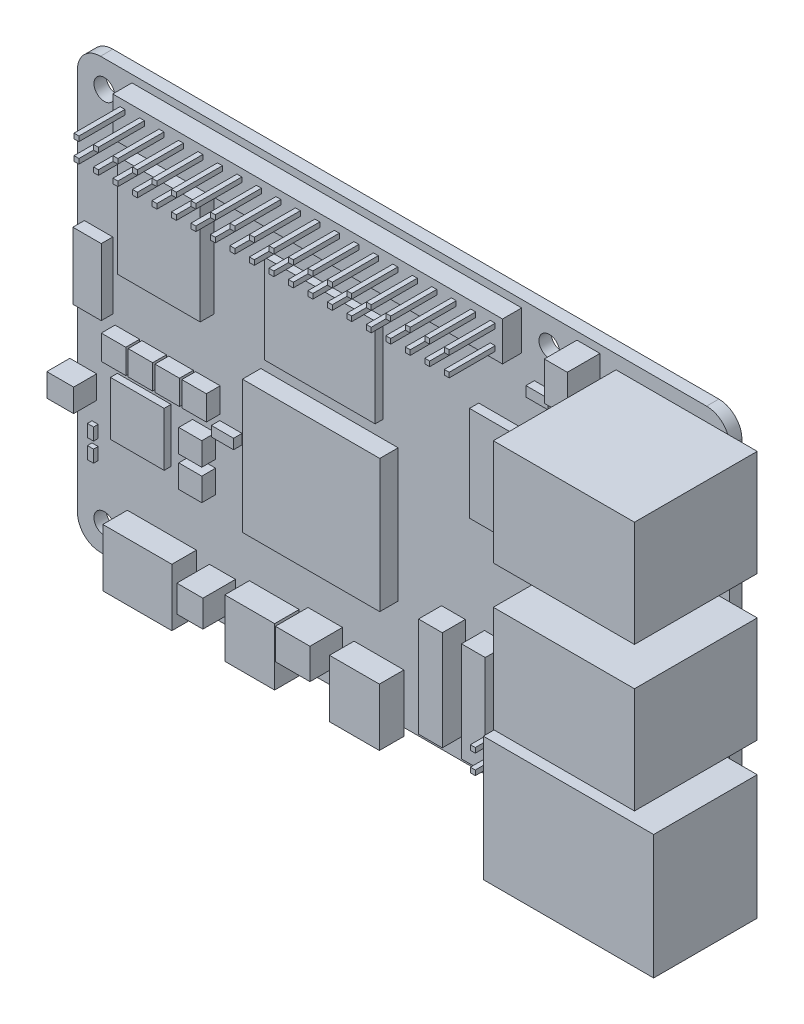
SolidWorks part; units mm, degrees
ref_plane "Front Plane" through (0, 0, 0) normal (0, 0, 1) x (1, 0, 0)
ref_plane "Top Plane" through (0, 0, 0) normal (0, 1, 0) x (1, 0, 0)
ref_plane "Right Plane" through (0, 0, 0) normal (1, 0, 0) x (0, 0, -1)
sketch "Sketch1" plane through (0, 0, 0) normal (0, 0, 1) x (1, 0, 0)
  line L0 (3, 0) -> (82, 0)
  line L1 (85, 3) -> (85, 53)
  line L2 (82, 56) -> (3, 56)
  line L3 (0, 53) -> (0, 3)
  arc A0 (82, 0) -> (85, 3) centre (82, 3) ccw
  arc A1 (85, 53) -> (82, 56) centre (82, 53) ccw
  arc A2 (3, 56) -> (0, 53) centre (3, 53) ccw
  arc A3 (0, 3) -> (3, 0) centre (3, 3) ccw
extrude "PCB" add sketch "Sketch1" along normal blind 1.6
ref_plane "Plane_z1_6" through (0, 0, 1.6) normal (0, 0, 1) x (1, 0, 0)
sketch "Sketch2" plane through (0, 0, 1.6) normal (0, 0, 1) x (1, 0, 0)
  line L1 (7.1, 49.96) -> (57.9, 49.96)
  line L2 (7.1, 49.96) -> (7.1, 55.04)
  line L3 (7.1, 55.04) -> (57.9, 55.04)
  line L4 (57.9, 49.96) -> (57.9, 55.04)
  line L6 (58.76, 6.76) -> (63.84, 6.76)
  line L7 (58.76, 6.76) -> (58.76, 11.84)
  line L8 (58.76, 11.84) -> (63.84, 11.84)
  line L9 (63.84, 6.76) -> (63.84, 11.84)
extrude "Header_Blocks" add sketch "Sketch2" along normal blind 2.5
ref_plane "Plane_z4_1" through (0, 0, 4.1) normal (0, 0, 1) x (1, 0, 0)
sketch "Sketch3" plane through (0, 0, 4.1) normal (0, 0, 1) x (1, 0, 0)
  line L1 (8.05, 50.91) -> (8.69, 50.91)
  line L2 (8.05, 50.91) -> (8.05, 51.55)
  line L3 (8.05, 51.55) -> (8.69, 51.55)
  line L4 (8.69, 50.91) -> (8.69, 51.55)
  line L6 (8.05, 53.45) -> (8.69, 53.45)
  line L7 (8.05, 53.45) -> (8.05, 54.09)
  line L8 (8.05, 54.09) -> (8.69, 54.09)
  line L9 (8.69, 53.45) -> (8.69, 54.09)
  line L11 (10.59, 50.91) -> (11.23, 50.91)
  line L12 (10.59, 50.91) -> (10.59, 51.55)
  line L13 (10.59, 51.55) -> (11.23, 51.55)
  line L14 (11.23, 50.91) -> (11.23, 51.55)
  line L16 (10.59, 53.45) -> (11.23, 53.45)
  line L17 (10.59, 53.45) -> (10.59, 54.09)
  line L18 (10.59, 54.09) -> (11.23, 54.09)
  line L19 (11.23, 53.45) -> (11.23, 54.09)
  line L21 (13.13, 50.91) -> (13.77, 50.91)
  line L22 (13.13, 50.91) -> (13.13, 51.55)
  line L23 (13.13, 51.55) -> (13.77, 51.55)
  line L24 (13.77, 50.91) -> (13.77, 51.55)
  line L26 (13.13, 53.45) -> (13.77, 53.45)
  line L27 (13.13, 53.45) -> (13.13, 54.09)
  line L28 (13.13, 54.09) -> (13.77, 54.09)
  line L29 (13.77, 53.45) -> (13.77, 54.09)
  line L31 (15.67, 50.91) -> (16.31, 50.91)
  line L32 (15.67, 50.91) -> (15.67, 51.55)
  line L33 (15.67, 51.55) -> (16.31, 51.55)
  line L34 (16.31, 50.91) -> (16.31, 51.55)
  line L36 (15.67, 53.45) -> (16.31, 53.45)
  line L37 (15.67, 53.45) -> (15.67, 54.09)
  line L38 (15.67, 54.09) -> (16.31, 54.09)
  line L39 (16.31, 53.45) -> (16.31, 54.09)
  line L41 (18.21, 50.91) -> (18.85, 50.91)
  line L42 (18.21, 50.91) -> (18.21, 51.55)
  line L43 (18.21, 51.55) -> (18.85, 51.55)
  line L44 (18.85, 50.91) -> (18.85, 51.55)
  line L46 (18.21, 53.45) -> (18.85, 53.45)
  line L47 (18.21, 53.45) -> (18.21, 54.09)
  line L48 (18.21, 54.09) -> (18.85, 54.09)
  line L49 (18.85, 53.45) -> (18.85, 54.09)
  line L51 (20.75, 50.91) -> (21.39, 50.91)
  line L52 (20.75, 50.91) -> (20.75, 51.55)
  line L53 (20.75, 51.55) -> (21.39, 51.55)
  line L54 (21.39, 50.91) -> (21.39, 51.55)
  line L56 (20.75, 53.45) -> (21.39, 53.45)
  line L57 (20.75, 53.45) -> (20.75, 54.09)
  line L58 (20.75, 54.09) -> (21.39, 54.09)
  line L59 (21.39, 53.45) -> (21.39, 54.09)
  line L61 (23.29, 50.91) -> (23.93, 50.91)
  line L62 (23.29, 50.91) -> (23.29, 51.55)
  line L63 (23.29, 51.55) -> (23.93, 51.55)
  line L64 (23.93, 50.91) -> (23.93, 51.55)
  line L66 (23.29, 53.45) -> (23.93, 53.45)
  line L67 (23.29, 53.45) -> (23.29, 54.09)
  line L68 (23.29, 54.09) -> (23.93, 54.09)
  line L69 (23.93, 53.45) -> (23.93, 54.09)
  line L71 (25.83, 50.91) -> (26.47, 50.91)
  line L72 (25.83, 50.91) -> (25.83, 51.55)
  line L73 (25.83, 51.55) -> (26.47, 51.55)
  line L74 (26.47, 50.91) -> (26.47, 51.55)
  line L76 (25.83, 53.45) -> (26.47, 53.45)
  line L77 (25.83, 53.45) -> (25.83, 54.09)
  line L78 (25.83, 54.09) -> (26.47, 54.09)
  line L79 (26.47, 53.45) -> (26.47, 54.09)
  line L81 (28.37, 50.91) -> (29.01, 50.91)
  line L82 (28.37, 50.91) -> (28.37, 51.55)
  line L83 (28.37, 51.55) -> (29.01, 51.55)
  line L84 (29.01, 50.91) -> (29.01, 51.55)
  line L86 (28.37, 53.45) -> (29.01, 53.45)
  line L87 (28.37, 53.45) -> (28.37, 54.09)
  line L88 (28.37, 54.09) -> (29.01, 54.09)
  line L89 (29.01, 53.45) -> (29.01, 54.09)
  line L91 (30.91, 50.91) -> (31.55, 50.91)
  line L92 (30.91, 50.91) -> (30.91, 51.55)
  line L93 (30.91, 51.55) -> (31.55, 51.55)
  line L94 (31.55, 50.91) -> (31.55, 51.55)
  line L96 (30.91, 53.45) -> (31.55, 53.45)
  line L97 (30.91, 53.45) -> (30.91, 54.09)
  line L98 (30.91, 54.09) -> (31.55, 54.09)
  line L99 (31.55, 53.45) -> (31.55, 54.09)
  line L101 (33.45, 50.91) -> (34.09, 50.91)
  line L102 (33.45, 50.91) -> (33.45, 51.55)
  line L103 (33.45, 51.55) -> (34.09, 51.55)
  line L104 (34.09, 50.91) -> (34.09, 51.55)
  line L106 (33.45, 53.45) -> (34.09, 53.45)
  line L107 (33.45, 53.45) -> (33.45, 54.09)
  line L108 (33.45, 54.09) -> (34.09, 54.09)
  line L109 (34.09, 53.45) -> (34.09, 54.09)
  line L111 (35.99, 50.91) -> (36.63, 50.91)
  line L112 (35.99, 50.91) -> (35.99, 51.55)
  line L113 (35.99, 51.55) -> (36.63, 51.55)
  line L114 (36.63, 50.91) -> (36.63, 51.55)
  line L116 (35.99, 53.45) -> (36.63, 53.45)
  line L117 (35.99, 53.45) -> (35.99, 54.09)
  line L118 (35.99, 54.09) -> (36.63, 54.09)
  line L119 (36.63, 53.45) -> (36.63, 54.09)
  line L121 (38.53, 50.91) -> (39.17, 50.91)
  line L122 (38.53, 50.91) -> (38.53, 51.55)
  line L123 (38.53, 51.55) -> (39.17, 51.55)
  line L124 (39.17, 50.91) -> (39.17, 51.55)
  line L126 (38.53, 53.45) -> (39.17, 53.45)
  line L127 (38.53, 53.45) -> (38.53, 54.09)
  line L128 (38.53, 54.09) -> (39.17, 54.09)
  line L129 (39.17, 53.45) -> (39.17, 54.09)
  line L131 (41.07, 50.91) -> (41.71, 50.91)
  line L132 (41.07, 50.91) -> (41.07, 51.55)
  line L133 (41.07, 51.55) -> (41.71, 51.55)
  line L134 (41.71, 50.91) -> (41.71, 51.55)
  line L136 (41.07, 53.45) -> (41.71, 53.45)
  line L137 (41.07, 53.45) -> (41.07, 54.09)
  line L138 (41.07, 54.09) -> (41.71, 54.09)
  line L139 (41.71, 53.45) -> (41.71, 54.09)
  line L141 (43.61, 50.91) -> (44.25, 50.91)
  line L142 (43.61, 50.91) -> (43.61, 51.55)
  line L143 (43.61, 51.55) -> (44.25, 51.55)
  line L144 (44.25, 50.91) -> (44.25, 51.55)
  line L146 (43.61, 53.45) -> (44.25, 53.45)
  line L147 (43.61, 53.45) -> (43.61, 54.09)
  line L148 (43.61, 54.09) -> (44.25, 54.09)
  line L149 (44.25, 53.45) -> (44.25, 54.09)
  line L151 (46.15, 50.91) -> (46.79, 50.91)
  line L152 (46.15, 50.91) -> (46.15, 51.55)
  line L153 (46.15, 51.55) -> (46.79, 51.55)
  line L154 (46.79, 50.91) -> (46.79, 51.55)
  line L156 (46.15, 53.45) -> (46.79, 53.45)
  line L157 (46.15, 53.45) -> (46.15, 54.09)
  line L158 (46.15, 54.09) -> (46.79, 54.09)
  line L159 (46.79, 53.45) -> (46.79, 54.09)
  line L161 (48.69, 50.91) -> (49.33, 50.91)
  line L162 (48.69, 50.91) -> (48.69, 51.55)
  line L163 (48.69, 51.55) -> (49.33, 51.55)
  line L164 (49.33, 50.91) -> (49.33, 51.55)
  line L166 (48.69, 53.45) -> (49.33, 53.45)
  line L167 (48.69, 53.45) -> (48.69, 54.09)
  line L168 (48.69, 54.09) -> (49.33, 54.09)
  line L169 (49.33, 53.45) -> (49.33, 54.09)
  line L171 (51.23, 50.91) -> (51.87, 50.91)
  line L172 (51.23, 50.91) -> (51.23, 51.55)
  line L173 (51.23, 51.55) -> (51.87, 51.55)
  line L174 (51.87, 50.91) -> (51.87, 51.55)
  line L176 (51.23, 53.45) -> (51.87, 53.45)
  line L177 (51.23, 53.45) -> (51.23, 54.09)
  line L178 (51.23, 54.09) -> (51.87, 54.09)
  line L179 (51.87, 53.45) -> (51.87, 54.09)
  line L181 (53.77, 50.91) -> (54.41, 50.91)
  line L182 (53.77, 50.91) -> (53.77, 51.55)
  line L183 (53.77, 51.55) -> (54.41, 51.55)
  line L184 (54.41, 50.91) -> (54.41, 51.55)
  line L186 (53.77, 53.45) -> (54.41, 53.45)
  line L187 (53.77, 53.45) -> (53.77, 54.09)
  line L188 (53.77, 54.09) -> (54.41, 54.09)
  line L189 (54.41, 53.45) -> (54.41, 54.09)
  line L191 (56.31, 50.91) -> (56.95, 50.91)
  line L192 (56.31, 50.91) -> (56.31, 51.55)
  line L193 (56.31, 51.55) -> (56.95, 51.55)
  line L194 (56.95, 50.91) -> (56.95, 51.55)
  line L196 (56.31, 53.45) -> (56.95, 53.45)
  line L197 (56.31, 53.45) -> (56.31, 54.09)
  line L198 (56.31, 54.09) -> (56.95, 54.09)
  line L199 (56.95, 53.45) -> (56.95, 54.09)
  line L201 (59.71, 7.71) -> (60.35, 7.71)
  line L202 (59.71, 7.71) -> (59.71, 8.35)
  line L203 (59.71, 8.35) -> (60.35, 8.35)
  line L204 (60.35, 7.71) -> (60.35, 8.35)
  line L206 (59.71, 10.25) -> (60.35, 10.25)
  line L207 (59.71, 10.25) -> (59.71, 10.89)
  line L208 (59.71, 10.89) -> (60.35, 10.89)
  line L209 (60.35, 10.25) -> (60.35, 10.89)
  line L211 (62.25, 7.71) -> (62.89, 7.71)
  line L212 (62.25, 7.71) -> (62.25, 8.35)
  line L213 (62.25, 8.35) -> (62.89, 8.35)
  line L214 (62.89, 7.71) -> (62.89, 8.35)
  line L216 (62.25, 10.25) -> (62.89, 10.25)
  line L217 (62.25, 10.25) -> (62.25, 10.89)
  line L218 (62.25, 10.89) -> (62.89, 10.89)
  line L219 (62.89, 10.25) -> (62.89, 10.89)
extrude "Header_Pins" add sketch "Sketch3" along normal blind 6
sketch "Sketch4" plane through (0, 0, 1.6) normal (0, 0, 1) x (1, 0, 0)
  line L1 (1.9, 10.2) -> (2.7, 10.2)
  line L2 (1.9, 10.2) -> (1.9, 11.8)
  line L3 (1.9, 11.8) -> (2.7, 11.8)
  line L4 (2.7, 10.2) -> (2.7, 11.8)
  line L6 (1.9, 12.7) -> (2.7, 12.7)
  line L7 (1.9, 12.7) -> (1.9, 14.3)
  line L8 (1.9, 14.3) -> (2.7, 14.3)
  line L9 (2.7, 12.7) -> (2.7, 14.3)
extrude "Parts_h0_6" add sketch "Sketch4" along normal blind 0.6
sketch "Sketch5" plane through (0, 0, 1.6) normal (0, 0, 1) x (1, 0, 0)
  line L0 (62.7, 19.918) -> (65.882, 23.1)
  line L1 (65.882, 23.1) -> (62.7, 26.282)
  line L2 (62.7, 26.282) -> (59.518, 23.1)
  line L3 (59.518, 23.1) -> (62.7, 19.918)
  line L5 (5.2, 14.3) -> (12.2, 14.3)
  line L6 (5.2, 14.3) -> (5.2, 21.3)
  line L7 (5.2, 21.3) -> (12.2, 21.3)
  line L8 (12.2, 14.3) -> (12.2, 21.3)
extrude "Parts_h0_9" add sketch "Sketch5" along normal blind 0.9
sketch "Sketch6" plane through (0, 0, 1.6) normal (0, 0, 1) x (1, 0, 0)
  line L1 (25.4, 33.4) -> (39.8, 33.4)
  line L2 (25.4, 33.4) -> (25.4, 45)
  line L3 (25.4, 45) -> (39.8, 45)
  line L4 (39.8, 33.4) -> (39.8, 45)
  line L6 (65.4, 43.35) -> (69.4, 43.35)
  line L7 (65.4, 43.35) -> (65.4, 47.85)
  line L8 (65.4, 47.85) -> (69.4, 47.85)
  line L9 (69.4, 43.35) -> (69.4, 47.85)
extrude "Parts_h1" add sketch "Sketch6" along normal blind 1
sketch "Sketch7" plane through (0, 0, 1.6) normal (0, 0, 1) x (1, 0, 0)
  line L1 (18.55, 21.35) -> (21.45, 21.35)
  line L2 (18.55, 21.35) -> (18.55, 22.65)
  line L3 (18.55, 22.65) -> (21.45, 22.65)
  line L4 (21.45, 21.35) -> (21.45, 22.65)
  line L6 (58.05, 17.35) -> (60.95, 17.35)
  line L7 (58.05, 17.35) -> (58.05, 18.65)
  line L8 (58.05, 18.65) -> (60.95, 18.65)
  line L9 (60.95, 17.35) -> (60.95, 18.65)
  line L11 (59.55, 46.35) -> (62.45, 46.35)
  line L12 (59.55, 46.35) -> (59.55, 47.65)
  line L13 (59.55, 47.65) -> (62.45, 47.65)
  line L14 (62.45, 46.35) -> (62.45, 47.65)
extrude "Parts_h1_1" add sketch "Sketch7" along normal blind 1.1
sketch "Sketch8" plane through (0, 0, 1.6) normal (0, 0, 1) x (1, 0, 0)
  line L1 (52.3, 29.1) -> (65.2, 29.1)
  line L2 (52.3, 29.1) -> (52.3, 41.5)
  line L3 (52.3, 41.5) -> (65.2, 41.5)
  line L4 (65.2, 29.1) -> (65.2, 41.5)
extrude "Parts_h1_2" add sketch "Sketch8" along normal blind 1.2
sketch "Sketch9" plane through (0, 0, 1.6) normal (0, 0, 1) x (1, 0, 0)
  line L1 (0.9, 27.7) -> (4.6, 27.7)
  line L2 (0.9, 27.7) -> (0.9, 36.4)
  line L3 (0.9, 36.4) -> (4.6, 36.4)
  line L4 (4.6, 27.7) -> (4.6, 36.4)
extrude "Parts_h1_5" add sketch "Sketch9" along normal blind 1.5
sketch "Sketch10" plane through (0, 0, 1.6) normal (0, 0, 1) x (1, 0, 0)
  line L1 (7, 34.3) -> (17.8, 34.3)
  line L2 (7, 34.3) -> (7, 47.6)
  line L3 (7, 47.6) -> (17.8, 47.6)
  line L4 (17.8, 34.3) -> (17.8, 47.6)
  line L6 (4.9, 23.4) -> (8.1, 23.4)
  line L7 (4.9, 23.4) -> (4.9, 26.6)
  line L8 (4.9, 26.6) -> (8.1, 26.6)
  line L9 (8.1, 23.4) -> (8.1, 26.6)
  line L11 (8.4, 23.4) -> (11.6, 23.4)
  line L12 (8.4, 23.4) -> (8.4, 26.6)
  line L13 (8.4, 26.6) -> (11.6, 26.6)
  line L14 (11.6, 23.4) -> (11.6, 26.6)
  line L16 (11.9, 23.4) -> (15.1, 23.4)
  line L17 (11.9, 23.4) -> (11.9, 26.6)
  line L18 (11.9, 26.6) -> (15.1, 26.6)
  line L19 (15.1, 23.4) -> (15.1, 26.6)
  line L21 (15.4, 23.4) -> (18.6, 23.4)
  line L22 (15.4, 23.4) -> (15.4, 26.6)
  line L23 (15.4, 26.6) -> (18.6, 26.6)
  line L24 (18.6, 23.4) -> (18.6, 26.6)
  line L26 (15, 18) -> (18, 18)
  line L27 (15, 18) -> (15, 21)
  line L28 (15, 21) -> (18, 21)
  line L29 (18, 18) -> (18, 21)
  line L31 (15, 14) -> (18, 14)
  line L32 (15, 14) -> (15, 17)
  line L33 (15, 17) -> (18, 17)
  line L34 (18, 14) -> (18, 17)
extrude "Parts_h1_8" add sketch "Sketch10" along normal blind 1.8
sketch "Sketch11" plane through (0, 0, 1.6) normal (0, 0, 1) x (1, 0, 0)
  line L1 (23.9, 13.9) -> (41.8, 13.9)
  line L2 (23.9, 13.9) -> (23.9, 31.2)
  line L3 (23.9, 31.2) -> (41.8, 31.2)
  line L4 (41.8, 13.9) -> (41.8, 31.2)
extrude "Parts_h2_4" add sketch "Sketch11" along normal blind 2.4
sketch "Sketch12" plane through (0, 0, 1.6) normal (0, 0, 1) x (1, 0, 0)
  line L1 (53.05, 3.2) -> (56.15, 3.2)
  line L2 (53.05, 3.2) -> (53.05, 16.2)
  line L3 (53.05, 16.2) -> (56.15, 16.2)
  line L4 (56.15, 3.2) -> (56.15, 16.2)
  line L6 (47.45, 3.2) -> (50.55, 3.2)
  line L7 (47.45, 3.2) -> (47.45, 16.2)
  line L8 (47.45, 16.2) -> (50.55, 16.2)
  line L9 (50.55, 3.2) -> (50.55, 16.2)
  line L11 (-1, 16.9) -> (2.5, 16.9)
  line L12 (-1, 16.9) -> (-1, 19.9)
  line L13 (-1, 19.9) -> (2.5, 19.9)
  line L14 (2.5, 16.9) -> (2.5, 19.9)
extrude "Parts_h3" add sketch "Sketch12" along normal blind 3
sketch "Sketch13" plane through (0, 0, 1.6) normal (0, 0, 1) x (1, 0, 0)
  line L1 (22.4, -1) -> (28.9, -1)
  line L2 (22.4, -1) -> (22.4, 6.5)
  line L3 (22.4, 6.5) -> (28.9, 6.5)
  line L4 (28.9, -1) -> (28.9, 6.5)
  line L6 (36.05, -1) -> (42.55, -1)
  line L7 (36.05, -1) -> (36.05, 6.5)
  line L8 (36.05, 6.5) -> (42.55, 6.5)
  line L9 (42.55, -1) -> (42.55, 6.5)
  line L11 (6.5, -1) -> (15.5, -1)
  line L12 (6.5, -1) -> (6.5, 6.5)
  line L13 (6.5, 6.5) -> (15.5, 6.5)
  line L14 (15.5, -1) -> (15.5, 6.5)
extrude "Parts_h3_2" add sketch "Sketch13" along normal blind 3.2
sketch "Sketch14" plane through (0, 0, 1.6) normal (0, 0, 1) x (1, 0, 0)
  line L1 (65.1, 50) -> (68.1, 50)
  line L2 (65.1, 50) -> (65.1, 55)
  line L3 (65.1, 55) -> (68.1, 55)
  line L4 (68.1, 50) -> (68.1, 55)
  line L6 (30.05, 3.3) -> (34.55, 3.3)
  line L7 (30.05, 3.3) -> (30.05, 7.3)
  line L8 (30.05, 7.3) -> (34.55, 7.3)
  line L9 (34.55, 3.3) -> (34.55, 7.3)
  line L11 (17.2, 2.25) -> (20.6, 2.25)
  line L12 (17.2, 2.25) -> (17.2, 5.75)
  line L13 (17.2, 5.75) -> (20.6, 5.75)
  line L14 (20.6, 2.25) -> (20.6, 5.75)
extrude "Parts_h4_25" add sketch "Sketch14" along normal blind 4.25
sketch "Sketch15" plane through (0, 0, 1.6) normal (0, 0, 1) x (1, 0, 0)
  line L1 (66.4, 1.5) -> (88.6, 1.5)
  line L2 (66.4, 1.5) -> (66.4, 17.7)
  line L3 (66.4, 17.7) -> (88.6, 17.7)
  line L4 (88.6, 1.5) -> (88.6, 17.7)
extrude "Parts_h13_5" add sketch "Sketch15" along normal blind 13.5
sketch "Sketch16" plane through (0, 0, 1.6) normal (0, 0, 1) x (1, 0, 0)
  line L1 (70.2, 40.4) -> (88.6, 40.4)
  line L2 (70.2, 40.4) -> (70.2, 54.2)
  line L3 (70.2, 54.2) -> (88.6, 54.2)
  line L4 (88.6, 40.4) -> (88.6, 54.2)
  line L6 (70.2, 21.6) -> (88.6, 21.6)
  line L7 (70.2, 21.6) -> (70.2, 35.4)
  line L8 (70.2, 35.4) -> (88.6, 35.4)
  line L9 (88.6, 21.6) -> (88.6, 35.4)
extrude "Parts_h16" add sketch "Sketch16" along normal blind 16
sketch "Sketch17" plane through (0, 0, 0) normal (0, 0, 1) x (1, 0, 0)
  circle A0 centre (3.5, 3.5) radius 1.35
  circle A1 centre (3.5, 52.5) radius 1.35
  circle A2 centre (61.5, 3.5) radius 1.35
  circle A3 centre (61.5, 52.5) radius 1.35
extrude "Mount_Holes" cut sketch "Sketch17" against normal through all and the other way through all
equation "\"pcb_l\" = 85mm"
equation "\"pcb_w\" = 56mm"
equation "\"pcb_t\" = 1.6mm"
equation "\"pcb_r\" = 3mm"
equation "\"hole_d\" = 2.7mm"
equation "\"hole_x1\" = 3.5mm"
equation "\"hole_x2\" = 61.5mm"
equation "\"hole_y1\" = 3.5mm"
equation "\"hole_y2\" = 52.5mm"
equation "\"hdr_pitch\" = 2.54mm"
equation "\"hdr_block_h\" = 2.5mm"
equation "\"hdr_pin\" = 0.64mm"
equation "\"hdr_pin_h\" = 6mm"
equation "\"gpio_x\" = 32.5mm"
equation "\"gpio_y\" = 52.5mm"
equation "\"poe_x\" = 61.3mm"
equation "\"poe_y\" = 9.3mm"
equation "\"D1@PCB\" = \"pcb_t\""
